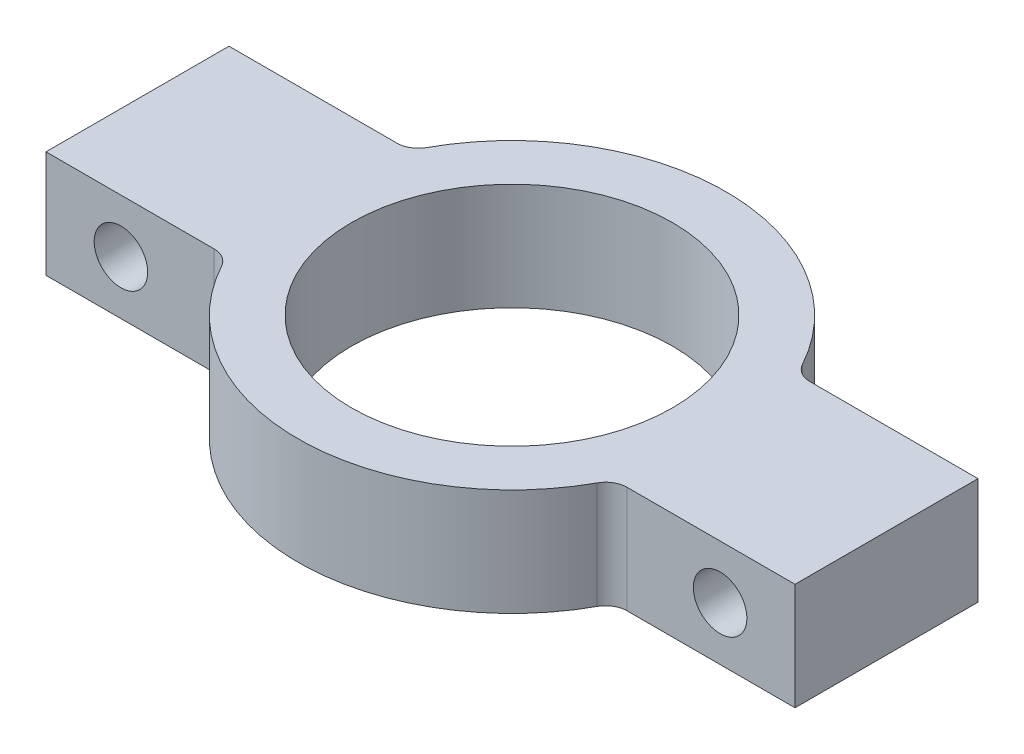
SolidWorks part; units mm, degrees
ref_plane "正面" through (0, 0, 0) normal (0, 0, 1) x (1, 0, 0)
ref_plane "平面" through (0, 0, 0) normal (0, 1, 0) x (1, 0, 0)
ref_plane "右側面" through (0, 0, 0) normal (1, 0, 0) x (0, 0, -1)
sketch "ｽｹｯﾁ1" plane through (0, 0, 0) normal (0, 1, 0) x (1, 0, 0)
  line L1 (-17.5, 4.275) -> (17.5, 4.275)
  line L2 (-17.5, 4.275) -> (-17.5, -4.275)
  line L3 (-17.5, -4.275) -> (17.5, -4.275)
  line L4 (17.5, 4.275) -> (17.5, -4.275)
  line L5 (-17.5, 4.275) -> (17.5, -4.275) construction
  line L6 (-17.5, -4.275) -> (17.5, 4.275) construction
  circle A0 centre (0, 0) radius 7.5
  circle A1 centre (0, 0) radius 10
  point P0 (0, 0)
  dimension "D3" = 15
  dimension "D1" = 8.55
  dimension "D2" = 35
  dimension "D4" = 2.5
extrude "ﾎﾞｽ - 押し出し1" add sketch "ｽｹｯﾁ1" along normal mid plane 5 contours A1 L1 L2 L3 | L1 A1 L3 A0 | L1 A1 A0 | L3 A1 L1 A0 | A1 L3 L4 L1 | L3 A1 A0 region at (-13.5881, 0, 0) region at (0, 0, -9.8103) region at (-8.3648, 0, 0) region at (8.3648, 0, 0) region at (13.5881, 0, 0) region at (-7.6012, 0, 4.4647)
sketch "ｽｹｯﾁ2" plane through (0, 0, -4.275) normal (0, 0, -1) x (-1, 0, 0)
  line L0 (9.0402, -2.5) -> (17.5, -2.5) construction
  line L1 (17.5, -2.5) -> (17.5, 2.5) construction
  line L2 (17.5, 2.5) -> (9.0402, 2.5) construction
  line L3 (9.0402, 2.5) -> (9.0402, -2.5) construction
  line L4 (-17.5, -2.5) -> (-9.0402, -2.5) construction
  line L5 (-9.0402, -2.5) -> (-9.0402, 2.5) construction
  line L6 (-9.0402, 2.5) -> (-17.5, 2.5) construction
  line L7 (-17.5, 2.5) -> (-17.5, -2.5) construction
  line L8 (9.0402, -2.5) -> (17.5, -2.5) construction
  line L9 (17.5, -2.5) -> (17.5, 2.5) construction
  line L10 (17.5, 2.5) -> (9.0402, 2.5) construction
  line L11 (9.0402, 2.5) -> (9.0402, -2.5) construction
  line L12 (-17.5, -2.5) -> (-9.0402, -2.5) construction
  line L13 (-9.0402, -2.5) -> (-9.0402, 2.5) construction
  line L14 (-9.0402, 2.5) -> (-17.5, 2.5) construction
  line L15 (-17.5, 2.5) -> (-17.5, -2.5) construction
  line L16 (-17.5, 0) -> (17.5, 0) construction
  line L17 (0, 0) -> (0, 2.5) construction
  line L18 (9.0402, 2.5) -> (-9.0402, 2.5) construction
  circle A0 centre (14, 0) radius 1.25
  circle A1 centre (-14, 0) radius 1.25
  dimension "D1" = 2.5
  dimension "D2" = 28
extrude "ｶｯﾄ - 押し出し1" cut sketch "ｽｹｯﾁ2" against normal blind 10
fillet "ﾌｨﾚｯﾄ1" radius 1 4 edges at (-9.0402, 0, -4.275) (9.0402, 0, -4.275) (9.0402, 0, 4.275) (-9.0402, 0, 4.275)
